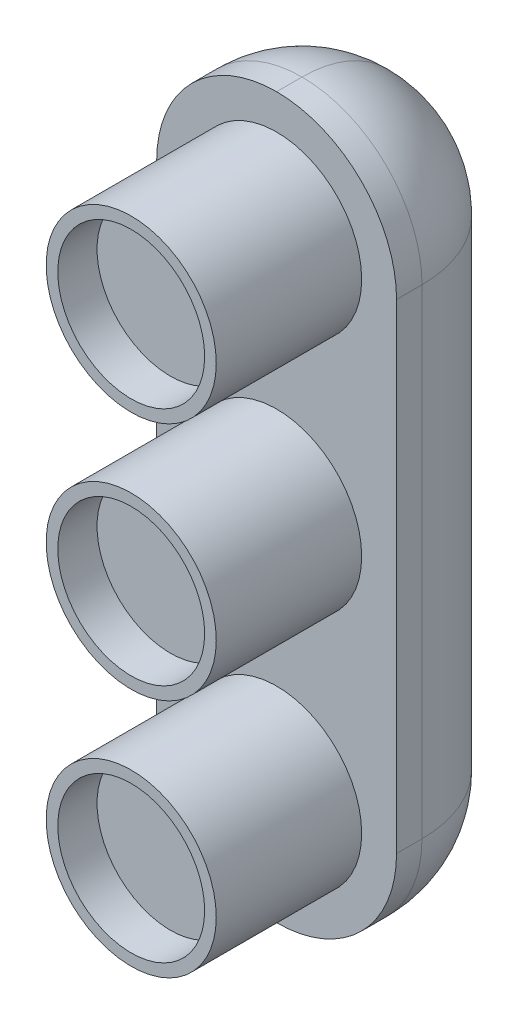
SolidWorks part; units mm, degrees
ref_plane "Ebene vorne" through (0, 0, 0) normal (0, 0, 1) x (1, 0, 0)
ref_plane "Ebene oben" through (0, 0, 0) normal (0, 1, 0) x (1, 0, 0)
ref_plane "Ebene rechts" through (0, 0, 0) normal (1, 0, 0) x (0, 0, -1)
sketch "Sketch1" plane through (0, 0, 0) normal (0, 0, 1) x (1, 0, 0)
  line L0 (-66, 165) -> (-49.5, 165)
  line L1 (0, 0) -> (-165, 0) construction
  line L2 (0, 0) -> (0, 165) construction
  line L3 (0, 165) -> (-165, 165) construction
  line L4 (-165, 0) -> (-165, 165) construction
  line L17 (-66, 165) -> (-66, 115.5)
  line L18 (-66, 115.5) -> (-49.5, 115.5)
  line L19 (-49.5, 165) -> (-49.5, 115.5)
  dimension "D1" = 165
  dimension "D2" = 165
  dimension "D12" = 49.5
  dimension "D13" = 16.5
extrude "Boss-Extrude1" add sketch "Sketch1" along normal blind 20
sketch "Sketch2" plane through (0, 0, 20) normal (0, 0, 1) x (1, 0, 0)
  line L0 (-66, 140.25) -> (-49.5, 140.25) construction
  line L1 (-66, 165) -> (-49.5, 165)
  line L2 (-66, 165) -> (-66, 115.5)
  line L3 (-66, 115.5) -> (-49.5, 115.5)
  line L4 (-49.5, 165) -> (-49.5, 115.5)
  circle A0 centre (-57.75, 156.75) radius 5.85
  circle A1 centre (-57.75, 140.25) radius 5.85
  circle A2 centre (-57.75, 156.75) radius 5.05
  circle A3 centre (-57.75, 140.25) radius 5.05
  circle A4 centre (-57.75, 123.75) radius 5.85
  circle A5 centre (-57.75, 123.75) radius 5.05
  point P13 (-57.75, 140.25)
  line M10 (-66, 165) -> (-66, 115.5)
  line M11 (-66, 115.5) -> (-49.5, 115.5)
  line M12 (-49.5, 115.5) -> (-49.5, 165)
  line M13 (-49.5, 165) -> (-66, 165)
  dimension "D1" = 16.5
  dimension "D2" = 11.7
  dimension "D3" = 11.7
  dimension "D4" = 10.1
extrude "Cut-Extrude1" cut sketch "Sketch2" against normal blind 10 contours L0 A1 L4 A0 M10 M13 | L0 L2 A1 A4 M11 M12 | A2 | L0 A3 | A3 L0 | A5 region at (-57.75, 138.1067, 20) region at (-57.75, 142.3933, 20) region at (-57.75, 146.3975, 20) region at (-50.7, 139.9525, 20) region at (-57.75, 156.75, 20) region at (-57.75, 123.75, 20)
fillet "Fillet1" radius 8.25 6 edges at (-66, 140.25, 0) (-49.5, 140.25, 0) (-66, 115.5, 5) (-49.5, 115.5, 5) (-66, 165, 5) (-49.5, 165, 5)
sketch "Sketch4" plane through (0, 0, 0) normal (0, 0, 1) x (1, 0, 0)
  circle A0 centre (-57.75, 156.75) radius 2.5
  circle A1 centre (-57.75, 140.25) radius 2.5
  circle A2 centre (-57.75, 123.75) radius 2.5
  dimension "D1" = 5
  dimension "D2" = 5
  dimension "D3" = 5
extrude "Cut-Extrude2" [suppressed] cut sketch "Sketch4" along normal blind 5
sketch "Sketch5" plane through (0, 0, 10) normal (0, 0, 1) x (1, 0, 0)
  circle A0 centre (-57.75, 156.75) radius 5.1
  circle A1 centre (-57.75, 140.25) radius 5.1
  circle A2 centre (-57.75, 123.75) radius 5.1
  dimension "D1" = 10.2
  dimension "D2" = 10.2
  dimension "D3" = 10.2
extrude "Boss-Extrude2" add sketch "Sketch5" along normal blind 7.3
